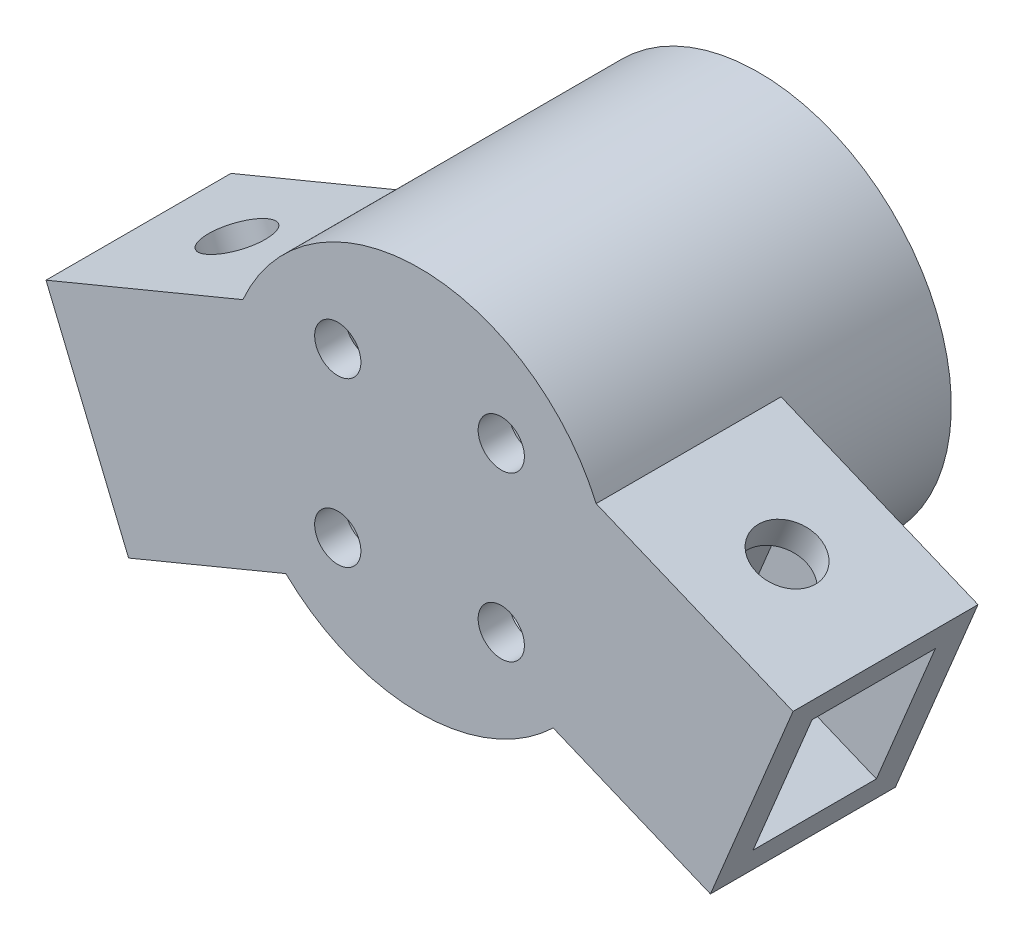
SolidWorks part; units mm, degrees
ref_plane "Front Plane" through (0, 0, 0) normal (0, 0, 1) x (1, 0, 0)
ref_plane "Top Plane" through (0, 0, 0) normal (0, 1, 0) x (1, 0, 0)
ref_plane "Right Plane" through (0, 0, 0) normal (1, 0, 0) x (0, 0, -1)
sketch "Sketch1" plane through (0, 0, 0) normal (0, 0, 1) x (1, 0, 0)
  line L0 (0, 0) -> (-12.5, 0) construction
  line L1 (0, 0) -> (-11.5485, -4.7835) construction
  line L2 (-20.7873, -8.6104) -> (-24.2314, -0.2955)
  line L3 (0, 0) -> (0, 11.25) construction
  line L4 (-20.7873, -8.6104) -> (-18.8739, -13.2298)
  line L5 (-18.8739, -13.2298) -> (-8.671, -9.0036)
  line L6 (-24.2314, -0.2955) -> (-11.4585, 4.9953)
  line L8 (18.8739, -13.2298) -> (8.671, -9.0036)
  line L9 (20.7873, -8.6104) -> (18.8739, -13.2298)
  line L12 (-20.7873, -8.6104) -> (-11.5485, -4.7835) construction
  line L13 (20.7873, -8.6104) -> (24.2314, -0.2955)
  line L14 (24.2314, -0.2955) -> (11.4585, 4.9953)
  circle A3 centre (0, 0) radius 12.5
  circle A4 centre (0, 0) radius 11.25
  dimension "D1" = 25
  dimension "D3" = 22.5
  dimension "D2" = 22.5
  dimension "D4" = 10
  dimension "D5" = 9
extrude "Boss-Extrude2" add sketch "Sketch1" along normal blind 12 contours A3
extrude "Cut-Extrude1" cut sketch "Sketch1<5>" along normal blind 10 contours A4
sketch "Sketch1<5>" plane through (0, 0, 0) normal (0, 0, 1) x (1, 0, 0) same geometry as "Sketch1"
sketch "Sketch4" plane through (0, 0, 12) normal (0, 0, 1) x (1, 0, 0)
  line L0 (0, 0) -> (0, 10) construction
  line L1 (0, 0) -> (10, 0) construction
  line L2 (0, 0) -> (10.6066, 10.6066) construction
  circle A1 centre (5.3033, 5.3033) radius 1.5
  circle A2 centre (-5.3033, 5.3033) radius 1.5
  circle A3 centre (-5.3033, -5.3033) radius 1.5
  circle A4 centre (5.3033, -5.3033) radius 1.5
  dimension "D1" = 3
  dimension "D2" = 15
extrude "Cut-Extrude2" cut sketch "Sketch4" against normal up to next
sketch "Sketch10" plane through (0, 0, 0) normal (0, 0, 1) x (1, 0, 0)
  line L0 (18.8739, -13.2298) -> (8.671, -9.0036) construction
  line L1 (20.7873, -8.6104) -> (18.8739, -13.2298) construction
  line L2 (20.7873, -8.6104) -> (24.2314, -0.2955) construction
  line L3 (24.2314, -0.2955) -> (11.4585, 4.9953) construction
  line L4 (-24.2314, -0.2955) -> (-11.4585, 4.9953) construction
  line L5 (-20.7873, -8.6104) -> (-24.2314, -0.2955) construction
  line L6 (-20.7873, -8.6104) -> (-18.8739, -13.2298) construction
  line L7 (-18.8739, -13.2298) -> (-8.671, -9.0036) construction
  line L8 (18.8739, -13.2298) -> (8.671, -9.0036)
  line L9 (20.7873, -8.6104) -> (18.8739, -13.2298)
  line L10 (20.7873, -8.6104) -> (24.2314, -0.2955)
  line L11 (24.2314, -0.2955) -> (11.4585, 4.9953)
  line L12 (-24.2314, -0.2955) -> (-11.4585, 4.9953)
  line L13 (-20.7873, -8.6104) -> (-24.2314, -0.2955)
  line L14 (-20.7873, -8.6104) -> (-18.8739, -13.2298)
  line L15 (-18.8739, -13.2298) -> (-8.671, -9.0036)
  arc A0 (8.671, -9.0036) -> (11.4585, 4.9953) centre (0, 0) ccw
  circle A3 centre (0, 0) radius 12.5
  arc A4 (-11.4585, 4.9953) -> (-8.671, -9.0036) centre (0, 0) ccw
  dimension "D2" = 0
extrude "Boss-Extrude3" add sketch "Sketch10" along normal blind 12
sketch "Sketch11" plane through (20.7873, -8.6104, 0) normal (0.9239, -0.3827, 0) x (0, 0, -1)
  line L0 (-12, 9) -> (0, 9) construction
  line L1 (-10, 7) -> (-2, 7)
  line L2 (-10, 7) -> (-10, -3)
  line L3 (-10, -3) -> (-2, -3)
  line L4 (-2, 7) -> (-2, -3)
  line L5 (-12, -5) -> (0, -5) construction
  line L6 (-12, -5) -> (-12, 9) construction
  line L7 (0, -5) -> (0, 9) construction
  dimension "D1" = 2
  dimension "D2" = 2
  dimension "D3" = 10
  dimension "D4" = 2
  dimension "D5" = 2
  dimension "D6" = 8
extrude "Cut-Extrude6" cut sketch "Sketch11" against normal blind 10
sketch "Sketch12" plane through (3.4442, 8.3149, 0) normal (0.3827, 0.9239, 0) x (0.9239, -0.3827, 0)
  line L0 (8.6747, -6) -> (22.5, -6) construction
  line L1 (8.6747, -12) -> (8.6747, 0) construction
  line L2 (22.5, -12) -> (22.5, 0) construction
  line L3 (15.5873, -12) -> (15.5873, 0) construction
  line L4 (22.5, -12) -> (8.6747, -12) construction
  line L5 (22.5, 0) -> (8.6747, 0) construction
  circle A2 centre (15.5873, -6) radius 2
extrude "Cut-Extrude7" cut sketch "Sketch12" against normal up to surface (14 mm away) up to face at (13.7724, -11.1167, 6)
mirror "Mirror5" about plane through (0, 0, 0) normal (1, 0, 0) of "Cut-Extrude6"
sketch "Sketch13" plane through (-3.4442, 8.3149, 0) normal (-0.3827, 0.9239, 0) x (0.9239, 0.3827, 0)
  line L0 (-8.6747, -6) -> (-22.5, -6) construction
  line L1 (-8.6747, -12) -> (-8.6747, 0) construction
  line L2 (-22.5, -12) -> (-22.5, 0) construction
  line L3 (-15.5873, 0) -> (-15.5873, -12) construction
  line L4 (-8.6747, 0) -> (-22.5, 0) construction
  line L5 (-8.6747, -12) -> (-22.5, -12) construction
  line L6 (-15.5873, -6) -> (-15.5873, -7) construction
  line L7 (-15.5873, -7) -> (-15.5873, -15) construction
  circle A2 centre (-15.5873, -6) radius 2
  dimension "D1" = 12
  dimension "D2" = 13.8253
extrude "Cut-Extrude8" cut sketch "Sketch13" against normal up to surface (14 mm away) up to face at (-13.7724, -11.1167, 6)
sketch "Sketch14" plane through (0, 0, 0) normal (0, 0, -1) x (-1, 0, 0)
  circle A0 centre (0, 0) radius 12.5
  circle A1 centre (0, 0) radius 11.25
  dimension "D1" = 22.5
extrude "Boss-Extrude4" add sketch "Sketch14" along normal blind 10
